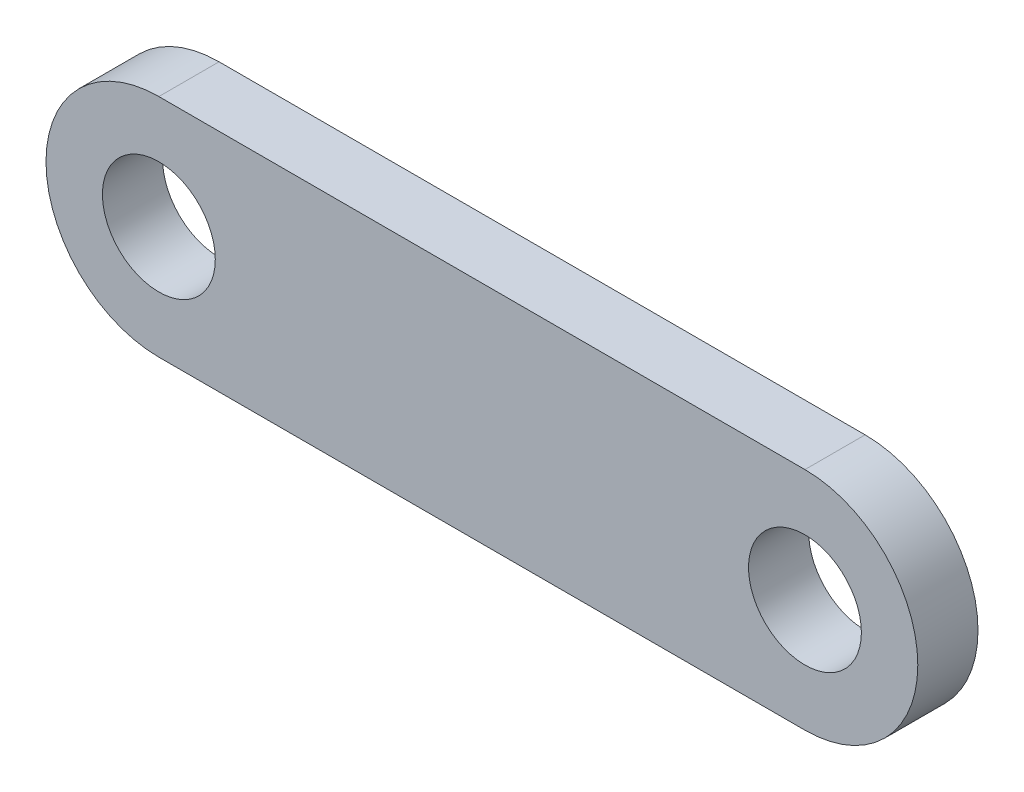
SolidWorks part; units mm, degrees
material "ABS"
ref_plane "Front Plane" through (0, 0, 0) normal (0, 0, 1) x (1, 0, 0)
ref_plane "Top Plane" through (0, 0, 0) normal (0, 1, 0) x (1, 0, 0)
ref_plane "Right Plane" through (0, 0, 0) normal (1, 0, 0) x (0, 0, -1)
sketch "Sketch1" plane through (0, 0, 0) normal (0, 0, 1) x (1, 0, 0)
  line L0 (0, 4.7625) -> (27.2644, 4.7625)
  line L1 (0, -4.7625) -> (27.2644, -4.7625)
  circle A0 centre (0, 0) radius 2.3813
  circle A1 centre (0, 0) radius 4.7625
  circle A2 centre (27.2644, 0) radius 2.3813
  circle A3 centre (27.2644, 0) radius 4.7625
  dimension "D1" = 4.7625
  dimension "D2" = 9.525
  dimension "D3" = 27.2644
extrude "Boss-Extrude2" add sketch "Sketch1" along normal blind 2.54 contours A1 A0 | A3 A2 | A3 L0 A1 L1 region at (13.6322, 0, 0) region at (3.2723, 3.2723, 0) region at (30.5367, 3.2723, 0)
